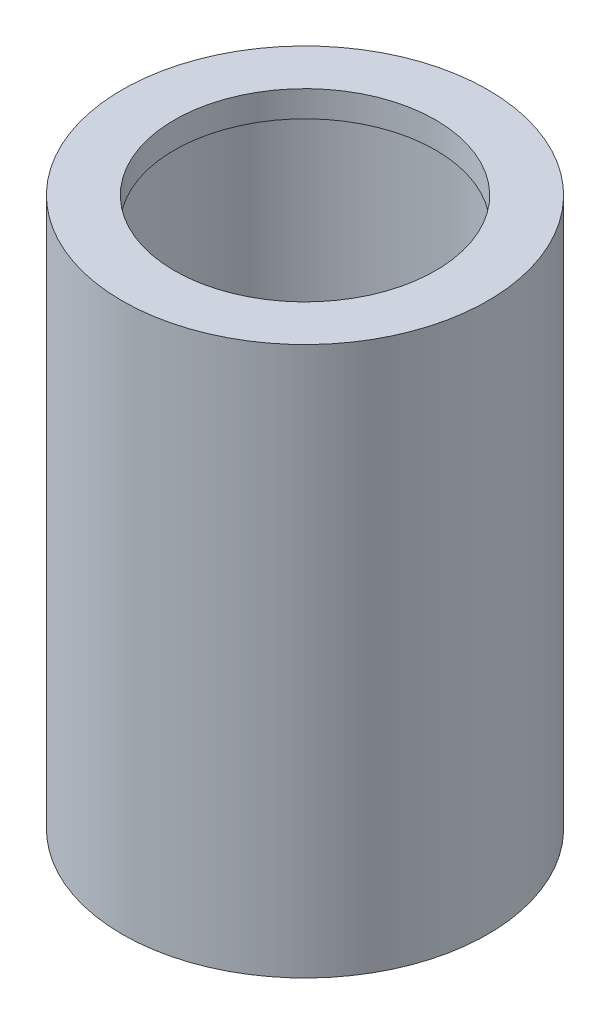
SolidWorks part; units mm, degrees
ref_plane "Front Plane" through (0, 0, 0) normal (0, 0, 1) x (1, 0, 0)
ref_plane "Top Plane" through (0, 0, 0) normal (0, 1, 0) x (1, 0, 0)
ref_plane "Right Plane" through (0, 0, 0) normal (1, 0, 0) x (0, 0, -1)
sketch "Sketch1" plane through (0, 0, 0) normal (0, 1, 0) x (1, 0, 0)
  circle A0 centre (0, 0) radius 35
  circle A1 centre (0, 0) radius 30
  dimension "D1" = 60
  dimension "D2" = 70
extrude "Boss-Extrude1" add sketch "Sketch1" along normal blind 100
ref_plane "Plane1" through (0, 100, 0) normal (0, 1, 0) x (1, 0, 0)
sketch "Sketch2" plane through (0, 100, 0) normal (0, 1, 0) x (1, 0, 0)
  circle A0 centre (0, 0) radius 25
  circle A1 centre (0, 0) radius 35
  dimension "D1" = 70
  dimension "D2" = 50
extrude "Boss-Extrude2" add sketch "Sketch2" along normal blind 5
equation "\"BallBearingDiameter\"= 22mm"
equation "\"SmallTubeOD\"= 50mm"
equation "\"SmallTubeID\"= \"SmallTubeOD\" - \"WallThickness\" * 2"
equation "\"ZTravel\"= 20mm"
equation "\"WallThickness\"= 5mm"
equation "\"RestrictingFlangeOD\"= \"SmallTubeOD\" + 10mm"
equation "\"D1@Sketch1\"=\"SmallTubeOD\" + \"WallThickness\"*2"
equation "\"D2@Sketch1\"=\"SmallTubeOD\"+\"WallThickness\"*4"
equation "\"D1@Sketch2\"=\"SmallTubeOD\"+\"WallThickness\"*4"
equation "\"D2@Sketch2\"=\"SmallTubeOD\""
equation "\"LargeTubeLength\"= 100mm"
equation "\"D1@Boss-Extrude1\"=\"LargeTubeLength\""
